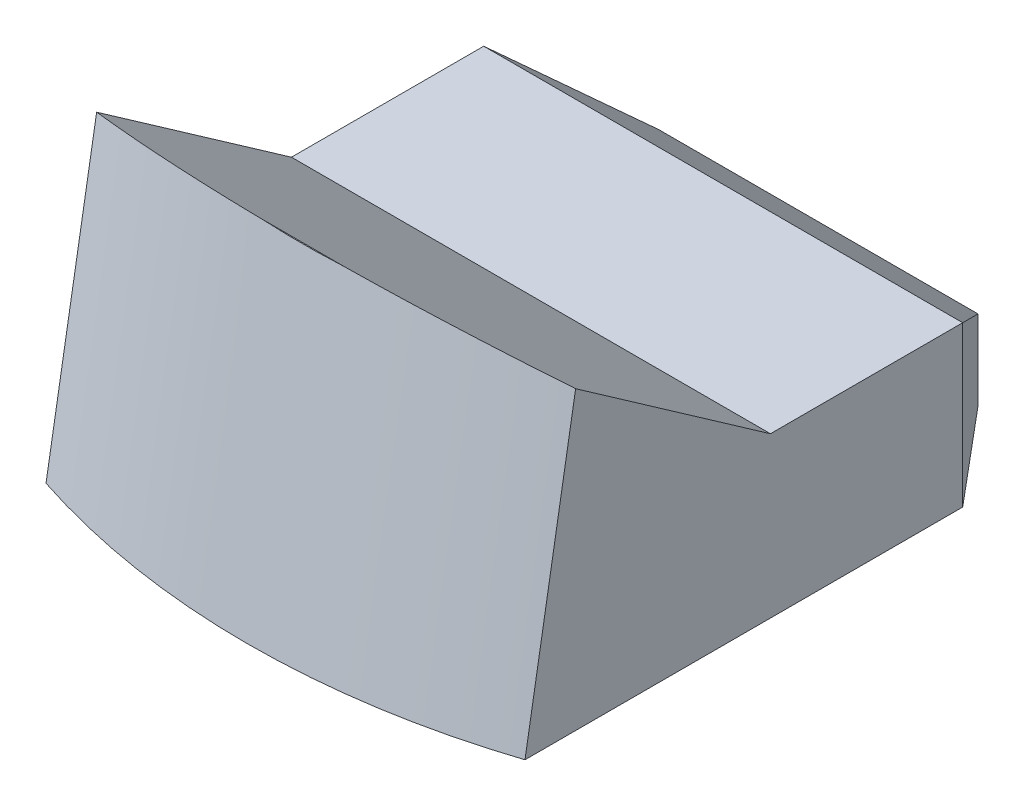
SolidWorks part; units mm, degrees
ref_plane "前视基准面" through (0, 0, 0) normal (0, 0, 1) x (1, 0, 0)
ref_plane "上视基准面" through (0, 0, 0) normal (0, 1, 0) x (1, 0, 0)
ref_plane "右视基准面" through (0, 0, 0) normal (1, 0, 0) x (0, 0, -1)
sketch "草图1" plane through (0, 0, 0) normal (0, 1, 0) x (1, 0, 0)
  line L5 (-1.5, 1) -> (1.5, 1)
  line L6 (-1.5, 1) -> (-1.5, -2.8)
  line L7 (-1.5, -2.8) -> (1.5, -2.8)
  line L8 (1.5, 1) -> (1.5, -2.8)
  point P4 (0, 1)
  dimension "D1" = 3
  dimension "D2" = 1
  dimension "D3" = 3.8
extrude "凸台-拉伸1" add sketch "草图1" along normal blind 1
sketch "草图2" plane through (0, 1, 0) normal (0, 1, 0) x (1, 0, 0)
  line L0 (1.5, -2.8) -> (1.5, 1) construction
  line L1 (-1.5, -2.8) -> (1.5, -2.8)
  line L2 (-1.5, -2.8) -> (-1.5, -0.8)
  line L3 (-1.5, -0.8) -> (1.5, -0.8)
  line L4 (1.5, -2.8) -> (1.5, -0.8)
  dimension "D1" = 2
extrude "凸台-拉伸2" add sketch "草图2" along normal blind 1
chamfer "倒角1" distance 0.5 angle 50 3 edges at (1.5, 0.5, -1) (-1.5, 0.5, -1) (0, 1, -1) first distance on face at (0, 0.5, -1)
sketch "草图3" plane through (0, 0, 2.8) normal (0, 0, 1) x (1, 0, 0)
  line L0 (-0.75, 1) -> (0.75, 1) construction
  line L1 (-0.75, 2) -> (0.75, 2)
  line L2 (-0.75, 0) -> (0.75, 0)
  line L3 (-1.5, 2) -> (1.5, 2) construction
  line L4 (-1.5, 0) -> (1.5, 0) construction
  line L5 (0, 1) -> (0, 0) construction
  arc A0 (-0.75, 2) -> (-0.75, 0) centre (-0.75, 1) ccw
  arc A1 (0.75, 0) -> (0.75, 2) centre (0.75, 1) ccw
  point P2 (0, 1)
  dimension "D1" = 1.5
chamfer "倒角3" distance 1 angle 55 1 edges at (0, 2, 0.8) first distance on face at (0, 1.5, 0.8)
sketch "草图4" plane through (0, 0, 0) normal (0, -1, 0) x (1, 0, 0)
  line L0 (1.6, 2.3034) -> (2.0905, 2.7939)
  line L1 (2.0905, 2.7939) -> (1.8452, 3.2653)
  line L2 (1.8452, 3.2653) -> (0.2787, 3.4688)
  line L3 (0.2787, 3.4688) -> (-0.1308, 3.4688)
  line L4 (-0.1308, 3.4688) -> (-1.9105, 3.4862)
  line L5 (-1.9105, 3.4862) -> (-2.191, 2.5703)
  line L6 (-2.191, 2.5703) -> (-1.6, 2.3034)
  arc A0 (1.6, 2.3034) -> (-1.6, 2.3034) centre (0, -2.2336) ccw construction
  arc A1 (1.6, 2.3034) -> (-1.6, 2.3034) centre (0, -2.2336) ccw
  point P7 (-1.9105, 3.4862)
sketch "草图6" plane through (1.5, 0, 0) normal (1, 0, 0) x (0, 0, -1)
  line L0 (-2.5703, 0) -> (-2.2281, 2) construction
  line L1 (-2.5703, 0) -> (-2.3034, 0) construction
  point P4 (0, 0)
extrude "切除-拉伸1" cut sketch "草图4" along direction (0, 0.9857, -0.1686) on the side against the normal blind 3.4 contours L4 L5 L6 A1 L0 L1 L2 L3
